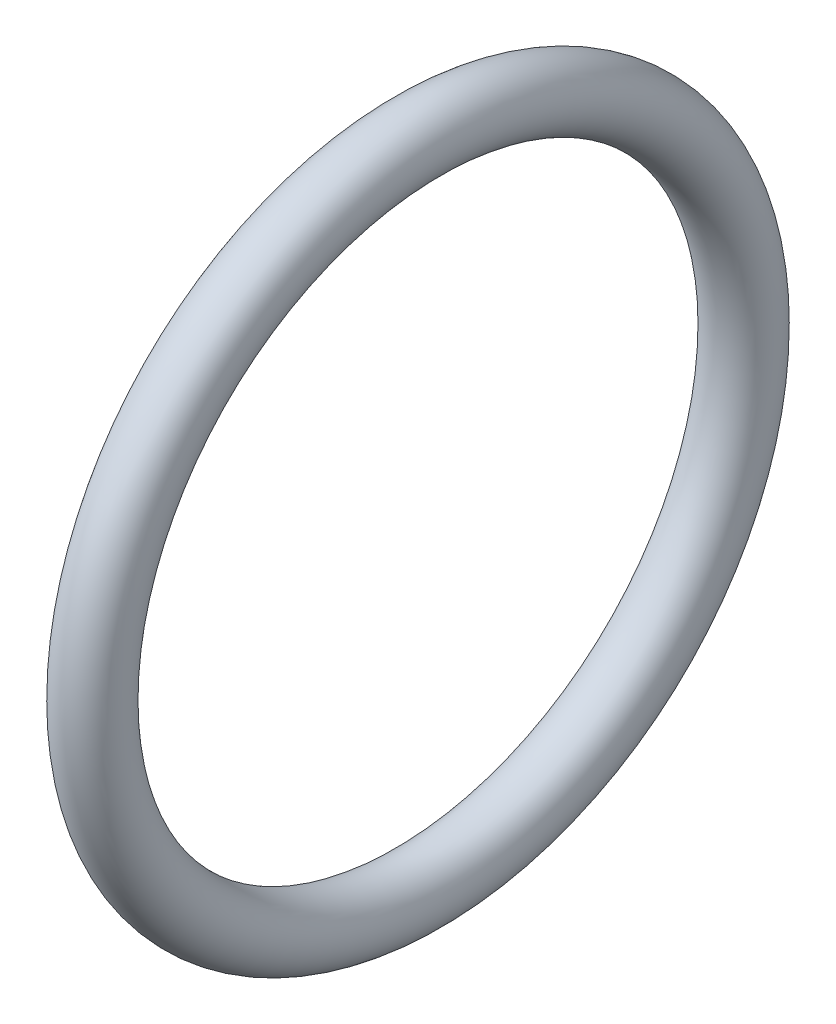
SolidWorks part; units mm, degrees
ref_plane "Plano frontal" through (0, 0, 0) normal (0, 0, 1) x (1, 0, 0)
ref_plane "Plano superior" through (0, 0, 0) normal (0, 1, 0) x (1, 0, 0)
ref_plane "Plano direito" through (0, 0, 0) normal (1, 0, 0) x (0, 0, -1)
sketch "Esboço1" plane through (0, 0, 0) normal (0, 0, 1) x (1, 0, 0)
  line L0 (0, 0) -> (0, 12.1) construction
  line L1 (0, 0) -> (21.9936, 0) construction
  circle A0 centre (0, 12.1) radius 1.2
  dimension "D1" = 2.4
  dimension "D2" = 12.1
revolve "Revolução1" add sketch "Esboço1" angle 360 about L1
ref_axis "Eixo1" through (-1.32, 0, 0) along (1, 0, 0)
